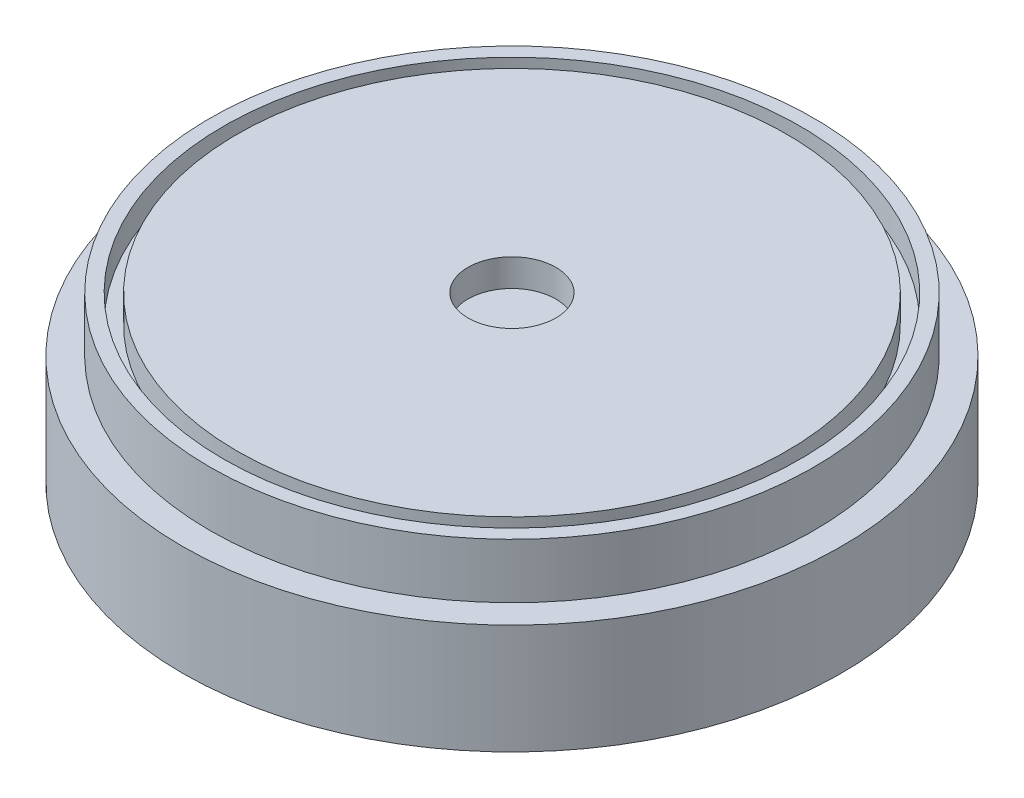
SolidWorks part; units mm, degrees
ref_plane "Front Plane" through (0, 0, 0) normal (0, 0, 1) x (1, 0, 0)
ref_plane "Top Plane" through (0, 0, 0) normal (0, 1, 0) x (1, 0, 0)
ref_plane "Right Plane" through (0, 0, 0) normal (1, 0, 0) x (0, 0, -1)
sketch "Sketch1" plane through (0, 0, 0) normal (0, 1, 0) x (1, 0, 0)
  circle A0 centre (0, 0) radius 120
  circle A1 centre (0, 0) radius 110
  circle A2 centre (0, 0) radius 100
  circle A3 centre (0, 0) radius 105
  dimension "D1" = 10
  dimension "D2" = 5
extrude "Boss-Extrude1" add sketch "Sketch1" along normal blind 40 contours A0
extrude "Boss-Extrude2" add sketch "Sketch1<3>" along normal blind 20 from surface contours A1 starting at face at (0, 40, 120)
sketch "Sketch1<3>" plane through (0, 0, 0) normal (0, 1, 0) x (1, 0, 0) same geometry as "Sketch1"
extrude "Cut-Extrude1" cut sketch "Sketch1<5>" against normal blind 10 from surface contours A3 A2 region at (-102.0302, 0, 0) starting at face at (0, 60, 110)
sketch "Sketch1<5>" plane through (0, 0, 0) normal (0, 1, 0) x (1, 0, 0) same geometry as "Sketch1"
sketch "Sketch2" plane through (0, 60, 0) normal (0, 1, 0) x (1, 0, 0)
  circle A0 centre (0, 0) radius 16
  dimension "D1" = 32
extrude "Cut-Extrude2" cut sketch "Sketch2" against normal blind 10
